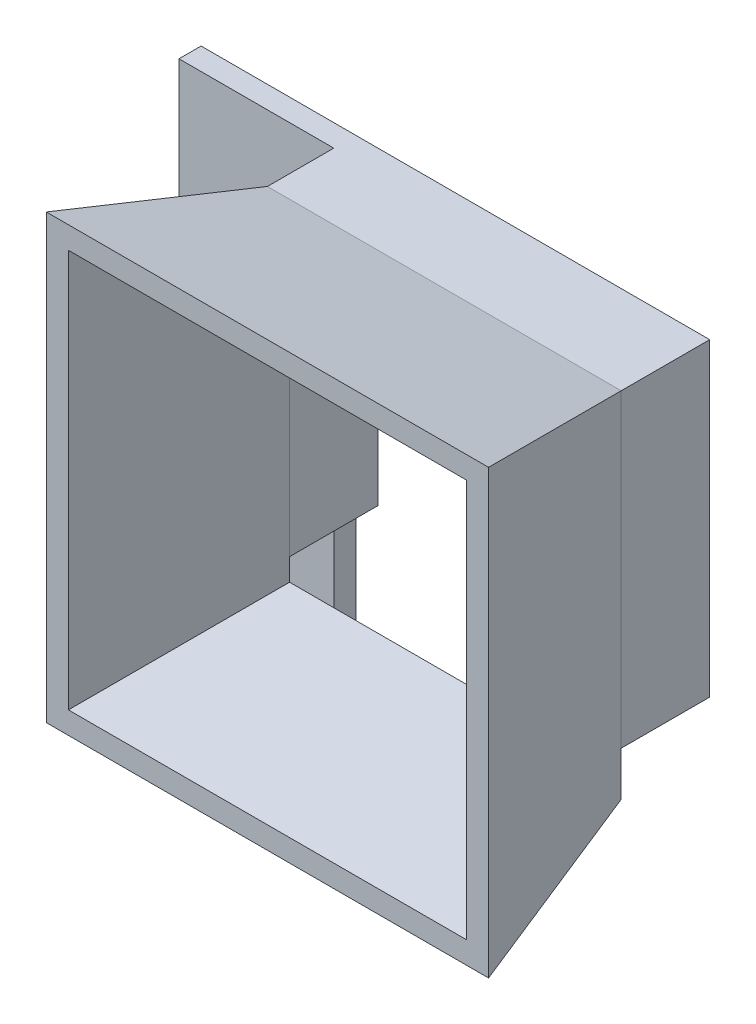
SolidWorks part; units mm, degrees
ref_plane "Front Plane" through (0, 0, 0) normal (0, 0, 1) x (1, 0, 0)
ref_plane "Top Plane" through (0, 0, 0) normal (0, 1, 0) x (1, 0, 0)
ref_plane "Right Plane" through (0, 0, 0) normal (1, 0, 0) x (0, 0, -1)
sketch "Sketch2" plane through (0, 0, 0) normal (0, 0, 1) x (1, 0, 0)
  line L0 (0, 0) -> (69.8407, 0) construction
  line L1 (-50.8, 50.8) -> (50.8, 50.8)
  line L2 (-50.8, 50.8) -> (-50.8, -50.8)
  line L3 (-50.8, -50.8) -> (50.8, -50.8)
  line L4 (50.8, 50.8) -> (50.8, -50.8)
  line L5 (0, 0) -> (0, -80.5593) construction
  dimension "D1" = 101.6
ref_plane "Plane1" through (0, 0, 50.8) normal (0, 0, 1) x (1, 0, 0)
sketch "Sketch3" plane through (0, 0, 50.8) normal (0, 0, 1) x (1, 0, 0)
  line L0 (0, 0) -> (0, 42.9934) construction
  line L1 (-63.5, 63.5) -> (63.5, 63.5)
  line L2 (-63.5, 63.5) -> (-63.5, -63.5)
  line L3 (-63.5, -63.5) -> (63.5, -63.5)
  line L4 (63.5, 63.5) -> (63.5, -63.5)
  line L7 (0, 0) -> (38.1349, 0) construction
  dimension "D1" = 127
loft "Loft1" add profiles "Sketch2", "Sketch3" connector at (50.8, 50.8, 0) connector at (63.5, 63.5, 50.8)
sketch "Sketch4" plane through (0, 0, 50.8) normal (0, 0, 1) x (1, 0, 0)
  line L14 (-57.15, -57.15) -> (57.15, -57.15)
  line L15 (57.15, -57.15) -> (57.15, 57.15)
  line L16 (57.15, 57.15) -> (-57.15, 57.15)
  line L17 (-57.15, 57.15) -> (-57.15, -57.15)
  line L18 (-57.15, -57.15) -> (57.15, -57.15)
  line L19 (57.15, -57.15) -> (57.15, 57.15)
  line L20 (57.15, 57.15) -> (-57.15, 57.15)
  line L21 (-57.15, 57.15) -> (-57.15, -57.15)
  dimension "D1" = 6.35
sketch "Sketch5" plane through (0, 0, 0) normal (0, 0, -1) x (-1, 0, 0)
  line L14 (-44.45, -44.45) -> (44.45, -44.45)
  line L15 (44.45, -44.45) -> (44.45, 44.45)
  line L16 (44.45, 44.45) -> (-44.45, 44.45)
  line L17 (-44.45, 44.45) -> (-44.45, -44.45)
  line L18 (-44.45, -44.45) -> (44.45, -44.45)
  line L19 (44.45, -44.45) -> (44.45, 44.45)
  line L20 (44.45, 44.45) -> (-44.45, 44.45)
  line L21 (-44.45, 44.45) -> (-44.45, -44.45)
  dimension "D1" = 6.35
loft "Cut-Loft1" cut profiles "Sketch5", "Sketch4" connector at (-44.45, 44.45, 0) connector at (-57.15, 57.15, 50.8)
sketch "Sketch6" plane through (0, 0, 0) normal (0, 0, -1) x (-1, 0, 0)
  line L0 (44.45, -38.1) -> (50.8, -38.1)
  line L1 (44.45, -44.45) -> (44.45, 44.45) construction
  line L2 (50.8, 50.8) -> (50.8, -50.8) construction
  line L3 (50.8, -38.1) -> (50.8, 50.8)
  line L4 (50.8, 50.8) -> (-50.8, 50.8)
  line L5 (-50.8, 50.8) -> (-50.8, -38.1)
  line L6 (-50.8, -50.8) -> (-50.8, 50.8) construction
  line L7 (-50.8, -38.1) -> (-44.45, -38.1)
  line L8 (-44.45, 44.45) -> (-44.45, -44.45) construction
  line L9 (-44.45, -38.1) -> (-44.45, 44.45)
  line L10 (-44.45, 44.45) -> (44.45, 44.45)
  line L11 (44.45, 44.45) -> (44.45, -38.1)
  line L12 (44.45, -38.1) -> (38.1, -38.1) construction
  line L13 (-44.45, -38.1) -> (-38.1, -38.1) construction
extrude "Boss-Extrude1" add sketch "Sketch6" along normal blind 25.4
sketch "Sketch7" plane through (0, 0, -25.4) normal (0, 0, -1) x (-1, 0, 0)
  line L0 (50.8, 50.8) -> (-50.8, 50.8) construction
  line L1 (44.45, -38.1) -> (95.25, -38.1)
  line L2 (44.45, -38.1) -> (44.45, 50.8)
  line L3 (44.45, 50.8) -> (95.25, 50.8)
  line L4 (95.25, -38.1) -> (95.25, 50.8)
  dimension "D1" = 50.8
extrude "Boss-Extrude2" add sketch "Sketch7" against normal blind 6.35
sketch "Sketch8" plane through (0, 0, -19.05) normal (0, 0, 1) x (1, 0, 0)
  line L0 (-50.8, 50.8) -> (-50.8, -38.1) construction
  line L1 (-95.25, -38.1) -> (-50.8, -38.1)
  line L2 (-95.25, -38.1) -> (-95.25, -76.2)
  line L3 (-95.25, -76.2) -> (-50.8, -76.2)
  line L4 (-50.8, -38.1) -> (-50.8, -76.2)
  dimension "D1" = 38.1
extrude "Boss-Extrude3" add sketch "Sketch8" against normal up to surface (6.35 mm away) up to face at (-11.1125, 4.7625, -25.4)
fillet "Fillet1" [suppressed] radius 35.56
sketch "Sketch9" plane through (0, 0, -19.05) normal (0, 0, 1) x (1, 0, 0)
  line L0 (-73.025, 27.6092) -> (-73.025, -57.5144) construction
  line L3 (-83.058, -50.3) -> (-83.058, -11.041) construction
  line L4 (-83.185, -10.3505) -> (-62.865, -10.3505)
  line L5 (-83.185, -10.3505) -> (-83.185, -50.9905)
  line L6 (-83.185, -50.9905) -> (-62.865, -50.9905)
  line L7 (-62.865, -10.3505) -> (-62.865, -50.9905)
  line L8 (-62.992, -11.041) -> (-62.992, -50.3) construction
  line L9 (-89.9768, -30.6705) -> (-55.7405, -30.6705) construction
  line L10 (-63.492, -50.8) -> (-82.558, -50.8) construction
  line L11 (-82.558, -10.541) -> (-63.492, -10.541) construction
  dimension "D1" = 20.32
  dimension "D2" = 40.64
fillet "Fillet2" [suppressed] radius 2.54
extrude "Cut-Extrude1" cut sketch "Sketch9" against normal through all
